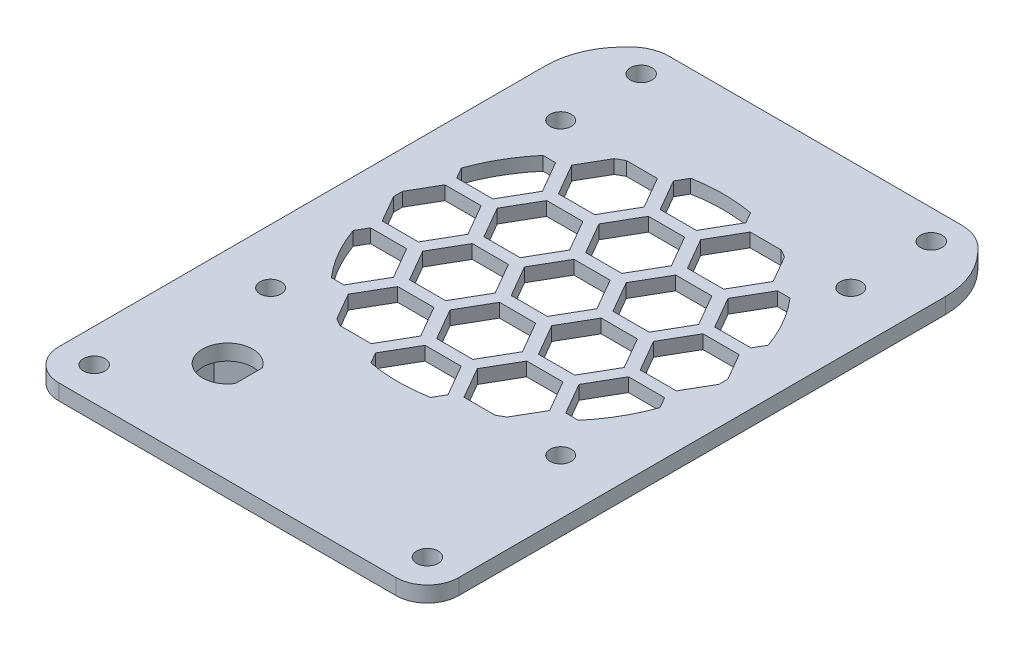
SolidWorks part; units mm, degrees
ref_plane "Front Plane" through (0, 0, 0) normal (0, 0, 1) x (1, 0, 0)
ref_plane "Top Plane" through (0, 0, 0) normal (0, 1, 0) x (1, 0, 0)
ref_plane "Right Plane" through (0, 0, 0) normal (1, 0, 0) x (0, 0, -1)
sketch "Sketch1" plane through (0, -8.5812, 0) normal (0, 1, 0) x (1, 0, 0)
  line L0 (-23.1823, 1.3362) -> (-42.1823, 1.3362)
  line L16 (-54.1823, -73.6638) -> (-11.1823, -73.6638)
  line L17 (-7.1823, -69.6638) -> (-7.1823, -7.6054)
  line L18 (-9.8717, -0.7822) -> (-11.849, 1.3362)
  line L19 (-11.849, 1.3362) -> (-23.1823, 1.3362)
  line L20 (-23.1823, 1.3362) -> (-23.1823, -1.1769)
  line L21 (-23.1823, -1.1769) -> (-10.589, -9.0704)
  line L22 (-9.1823, -11.6123) -> (-9.1823, -59.6638)
  line L23 (-9.1823, -59.6638) -> (-21.1823, -71.6638)
  line L24 (-21.1823, -71.6638) -> (-44.1823, -71.6638)
  line L25 (-44.1823, -71.6638) -> (-56.1823, -59.6638)
  line L26 (-56.1823, -59.6638) -> (-56.1823, -11.6123)
  line L27 (-54.7756, -9.0704) -> (-42.1823, -1.1769)
  line L28 (-42.1823, -1.1769) -> (-42.1823, 1.3362)
  line L29 (-42.1823, 1.3362) -> (-53.5156, 1.3362)
  line L30 (-53.5156, 1.3362) -> (-55.4928, -0.7822)
  line L31 (-58.1823, -7.6054) -> (-58.1823, -69.6638)
  line L32 (-54.1823, -73.6638) -> (-11.1823, -73.6638)
  line L33 (-7.1823, -69.6638) -> (-7.1823, -7.6054)
  line L34 (-9.8717, -0.7822) -> (-11.849, 1.3362)
  line L35 (-11.849, 1.3362) -> (-23.1823, 1.3362)
  line L36 (-23.1823, 1.3362) -> (-23.1823, -1.1769)
  line L37 (-23.1823, -1.1769) -> (-10.589, -9.0704)
  line L38 (-9.1823, -11.6123) -> (-9.1823, -59.6638)
  line L39 (-9.1823, -59.6638) -> (-21.1823, -71.6638)
  line L40 (-21.1823, -71.6638) -> (-44.1823, -71.6638)
  line L41 (-44.1823, -71.6638) -> (-56.1823, -59.6638)
  line L42 (-56.1823, -59.6638) -> (-56.1823, -11.6123)
  line L43 (-54.7756, -9.0704) -> (-42.1823, -1.1769)
  line L44 (-42.1823, -1.1769) -> (-42.1823, 1.3362)
  line L45 (-42.1823, 1.3362) -> (-53.5156, 1.3362)
  line L46 (-53.5156, 1.3362) -> (-55.4928, -0.7822)
  line L47 (-58.1823, -7.6054) -> (-58.1823, -69.6638)
  circle A0 centre (-14.1823, -2.3941) radius 1.375
  circle A1 centre (-51.1823, -2.3941) radius 1.375
  circle A2 centre (-11.4323, -69.4138) radius 1.375
  circle A3 centre (-53.9323, -69.4138) radius 1.375
  arc A6 (-11.1823, -73.6638) -> (-7.1823, -69.6638) centre (-11.1823, -69.6638) ccw
  arc A7 (-7.1823, -7.6054) -> (-9.8717, -0.7822) centre (-17.1823, -7.6054) ccw
  arc A8 (-9.1823, -11.6123) -> (-10.589, -9.0704) centre (-12.1823, -11.6123) ccw
  arc A9 (-54.7756, -9.0704) -> (-56.1823, -11.6123) centre (-53.1823, -11.6123) ccw
  arc A10 (-55.4928, -0.7822) -> (-58.1823, -7.6054) centre (-48.1823, -7.6054) ccw
  arc A11 (-58.1823, -69.6638) -> (-54.1823, -73.6638) centre (-54.1823, -69.6638) ccw
  arc A12 (-11.1823, -73.6638) -> (-7.1823, -69.6638) centre (-11.1823, -69.6638) ccw
  arc A13 (-7.1823, -7.6054) -> (-9.8717, -0.7822) centre (-17.1823, -7.6054) ccw
  arc A14 (-9.1823, -11.6123) -> (-10.589, -9.0704) centre (-12.1823, -11.6123) ccw
  arc A15 (-54.7756, -9.0704) -> (-56.1823, -11.6123) centre (-53.1823, -11.6123) ccw
  arc A16 (-55.4928, -0.7822) -> (-58.1823, -7.6054) centre (-48.1823, -7.6054) ccw
  arc A17 (-58.1823, -69.6638) -> (-54.1823, -73.6638) centre (-54.1823, -69.6638) ccw
  circle M24 centre (-51.1823, -2.3941) radius 2.3
  circle M25 centre (-11.4323, -69.4138) radius 2.3
  circle M26 centre (-53.9323, -69.4138) radius 2.3
  circle M27 centre (-14.1823, -2.3941) radius 2.3
  line M28 (-54.1823, -73.6638) -> (-11.1823, -73.6638)
  arc M29 (-11.1823, -73.6638) -> (-7.1823, -69.6638) centre (-11.1823, -69.6638) ccw
  line M30 (-7.1823, -69.6638) -> (-7.1823, -7.6054)
  arc M31 (-7.1823, -7.6054) -> (-9.8717, -0.7822) centre (-17.1823, -7.6054) ccw
  line M32 (-9.8717, -0.7822) -> (-11.849, 1.3362)
  line M33 (-11.849, 1.3362) -> (-23.1823, 1.3362)
  line M34 (-23.1823, 1.3362) -> (-23.1823, -1.1769)
  line M35 (-23.1823, -1.1769) -> (-10.589, -9.0704)
  arc M36 (-10.589, -9.0704) -> (-9.1823, -11.6123) centre (-12.1823, -11.6123) cw
  line M37 (-9.1823, -11.6123) -> (-9.1823, -59.6638)
  line M38 (-9.1823, -59.6638) -> (-21.1823, -71.6638)
  line M39 (-21.1823, -71.6638) -> (-44.1823, -71.6638)
  line M40 (-44.1823, -71.6638) -> (-56.1823, -59.6638)
  line M41 (-56.1823, -59.6638) -> (-56.1823, -11.6123)
  arc M42 (-56.1823, -11.6123) -> (-54.7756, -9.0704) centre (-53.1823, -11.6123) cw
  line M43 (-54.7756, -9.0704) -> (-42.1823, -1.1769)
  line M44 (-42.1823, -1.1769) -> (-42.1823, 1.3362)
  line M45 (-42.1823, 1.3362) -> (-53.5156, 1.3362)
  line M46 (-53.5156, 1.3362) -> (-55.4928, -0.7822)
  arc M47 (-55.4928, -0.7822) -> (-58.1823, -7.6054) centre (-48.1823, -7.6054) ccw
  line M48 (-58.1823, -7.6054) -> (-58.1823, -69.6638)
  arc M49 (-58.1823, -69.6638) -> (-54.1823, -73.6638) centre (-54.1823, -69.6638) ccw
  dimension "D2" = 2.75
  dimension "D3" = 2.75
  dimension "D4" = 2.75
  dimension "D5" = 2.75
  dimension "D1" = 0
extrude "Boss-Extrude1" add sketch "Sketch1" along normal blind 2 contours M49 M28 M29 M30 M31 M32 M33 M34 M35 M36 M37 M38 M39 M40 M41 M42 M43 M44 M45 M46 M47 M48 M25 M27 M26 M24 | L0 M34 M44 M43 M42 M41 M40 M39 M38 M37 M36 M35 | A0 M27 | A1 M24 | A3 M26 | A2 M25 region at (-32.6823, -8.5812, 35.6933) region at (-17.5156, -8.5812, -0.4292) region at (-53.4172, -8.5812, 2.3941) region at (-13.6672, -8.5812, 69.4138) region at (-56.1672, -8.5812, 69.4138) region at (-16.4172, -8.5812, 2.3941)
fillet "Fillet1" radius 5 2 edges at (-11.849, -7.5812, -1.3362) (-53.5156, -7.5812, -1.3362)
sketch "Sketch2" plane through (0, -6.5812, 0) normal (0, 1, 0) x (1, 0, 0)
  circle A1 centre (-32.6823, -31.1638) radius 20.75
  circle A2 centre (-32.6823, -31.1638) radius 20.75
  dimension "D1" = 0
extrude "Cut-Extrude1" cut sketch "Sketch2" against normal through all
sketch "Sketch3" plane through (0, -8.5812, 0) normal (0, -1, 0) x (1, 0, 0)
  circle A2 centre (-32.6823, 31.1638) radius 21.75
  circle A3 centre (-32.6823, 31.1638) radius 21.75
  dimension "D1" = 1
extrude "Cut-Extrude2" cut sketch "Sketch3" against normal blind 0.25
sketch "Sketch4" plane through (0, -6.5812, 0) normal (0, 1, 0) x (1, 0, 0)
  line L0 (-49.1368, -12.1638) -> (-40.9095, -16.9138) construction
  line L1 (-38.6001, -12.9138) -> (-43.2189, -12.9138)
  line L2 (-43.2189, -12.9138) -> (-45.5283, -16.9138)
  line L3 (-45.5283, -16.9138) -> (-43.2189, -20.9138)
  line L4 (-43.2189, -20.9138) -> (-38.6001, -20.9138)
  line L5 (-38.6001, -20.9138) -> (-36.2907, -16.9138)
  line L6 (-36.2907, -16.9138) -> (-38.6001, -12.9138)
  line L7 (-44.518, -12.1638) -> (-46.8274, -8.1638)
  line L8 (-46.8274, -8.1638) -> (-51.4462, -8.1638)
  line L9 (-51.4462, -8.1638) -> (-53.7556, -12.1638)
  line L10 (-53.7556, -12.1638) -> (-51.4462, -16.1638)
  line L11 (-51.4462, -16.1638) -> (-46.8274, -16.1638)
  line L12 (-46.8274, -16.1638) -> (-44.518, -12.1638)
  line L13 (-22.1456, -12.9138) -> (-26.7644, -12.9138)
  line L14 (-26.7644, -12.9138) -> (-29.0738, -16.9138)
  line L15 (-29.0738, -16.9138) -> (-26.7644, -20.9138)
  line L16 (-26.7644, -20.9138) -> (-22.1456, -20.9138)
  line L17 (-22.1456, -20.9138) -> (-19.8362, -16.9138)
  line L18 (-19.8362, -16.9138) -> (-22.1456, -12.9138)
  line L19 (-28.0635, -12.1638) -> (-30.3729, -8.1638)
  line L20 (-34.9917, -8.1638) -> (-37.3011, -12.1638)
  line L21 (-37.3011, -12.1638) -> (-34.9917, -16.1638)
  line L22 (-34.9917, -16.1638) -> (-30.3729, -16.1638)
  line L23 (-30.3729, -16.1638) -> (-28.0635, -12.1638)
  line L24 (-32.6823, -12.1638) -> (-24.455, -16.9138) construction
  line L25 (-30.3729, -8.1638) -> (-34.9917, -8.1638)
  line L26 (-5.6912, -12.9138) -> (-10.31, -12.9138)
  line L27 (-10.31, -12.9138) -> (-12.6194, -16.9138)
  line L28 (-12.6194, -16.9138) -> (-10.31, -20.9138)
  line L29 (-10.31, -20.9138) -> (-5.6912, -20.9138)
  line L30 (-5.6912, -20.9138) -> (-3.3818, -16.9138)
  line L31 (-3.3818, -16.9138) -> (-5.6912, -12.9138)
  line L32 (-11.609, -12.1638) -> (-13.9184, -8.1638)
  line L33 (-18.5372, -8.1638) -> (-20.8466, -12.1638)
  line L34 (-20.8466, -12.1638) -> (-18.5372, -16.1638)
  line L35 (-18.5372, -16.1638) -> (-13.9184, -16.1638)
  line L36 (-13.9184, -16.1638) -> (-11.609, -12.1638)
  line L37 (-16.2278, -12.1638) -> (-8.0006, -16.9138) construction
  line L38 (-13.9184, -8.1638) -> (-18.5372, -8.1638)
  line L39 (-22.1456, -22.4138) -> (-26.7644, -22.4138)
  line L40 (-26.7644, -22.4138) -> (-29.0738, -26.4138)
  line L41 (-29.0738, -26.4138) -> (-26.7644, -30.4138)
  line L42 (-26.7644, -30.4138) -> (-22.1456, -30.4138)
  line L43 (-22.1456, -30.4138) -> (-19.8362, -26.4138)
  line L44 (-19.8362, -26.4138) -> (-22.1456, -22.4138)
  line L45 (-28.0635, -21.6638) -> (-30.3729, -17.6638)
  line L46 (-34.9917, -17.6638) -> (-37.3011, -21.6638)
  line L47 (-37.3011, -21.6638) -> (-34.9917, -25.6638)
  line L48 (-34.9917, -25.6638) -> (-30.3729, -25.6638)
  line L49 (-30.3729, -25.6638) -> (-28.0635, -21.6638)
  line L50 (-32.6823, -21.6638) -> (-24.455, -26.4138) construction
  line L51 (-30.3729, -17.6638) -> (-34.9917, -17.6638)
  line L52 (-5.6912, -22.4138) -> (-10.31, -22.4138)
  line L53 (-10.31, -22.4138) -> (-12.6194, -26.4138)
  line L54 (-12.6194, -26.4138) -> (-10.31, -30.4138)
  line L55 (-10.31, -30.4138) -> (-5.6912, -30.4138)
  line L56 (-5.6912, -30.4138) -> (-3.3818, -26.4138)
  line L57 (-3.3818, -26.4138) -> (-5.6912, -22.4138)
  line L58 (-11.609, -21.6638) -> (-13.9184, -17.6638)
  line L59 (-18.5372, -17.6638) -> (-20.8466, -21.6638)
  line L60 (-20.8466, -21.6638) -> (-18.5372, -25.6638)
  line L61 (-18.5372, -25.6638) -> (-13.9184, -25.6638)
  line L62 (-13.9184, -25.6638) -> (-11.609, -21.6638)
  line L63 (-16.2278, -21.6638) -> (-8.0006, -26.4138) construction
  line L64 (-13.9184, -17.6638) -> (-18.5372, -17.6638)
  line L65 (-22.1456, -31.9138) -> (-26.7644, -31.9138)
  line L66 (-26.7644, -31.9138) -> (-29.0738, -35.9138)
  line L67 (-29.0738, -35.9138) -> (-26.7644, -39.9138)
  line L68 (-26.7644, -39.9138) -> (-22.1456, -39.9138)
  line L69 (-22.1456, -39.9138) -> (-19.8362, -35.9138)
  line L70 (-19.8362, -35.9138) -> (-22.1456, -31.9138)
  line L71 (-28.0635, -31.1638) -> (-30.3729, -27.1638)
  line L72 (-34.9917, -27.1638) -> (-37.3011, -31.1638)
  line L73 (-37.3011, -31.1638) -> (-34.9917, -35.1638)
  line L74 (-34.9917, -35.1638) -> (-30.3729, -35.1638)
  line L75 (-30.3729, -35.1638) -> (-28.0635, -31.1638)
  line L76 (-32.6823, -31.1638) -> (-24.455, -35.9138) construction
  line L77 (-30.3729, -27.1638) -> (-34.9917, -27.1638)
  line L78 (-5.6912, -31.9138) -> (-10.31, -31.9138)
  line L79 (-10.31, -31.9138) -> (-12.6194, -35.9138)
  line L80 (-12.6194, -35.9138) -> (-10.31, -39.9138)
  line L81 (-10.31, -39.9138) -> (-5.6912, -39.9138)
  line L82 (-5.6912, -39.9138) -> (-3.3818, -35.9138)
  line L83 (-3.3818, -35.9138) -> (-5.6912, -31.9138)
  line L84 (-11.609, -31.1638) -> (-13.9184, -27.1638)
  line L85 (-18.5372, -27.1638) -> (-20.8466, -31.1638)
  line L86 (-20.8466, -31.1638) -> (-18.5372, -35.1638)
  line L87 (-18.5372, -35.1638) -> (-13.9184, -35.1638)
  line L88 (-13.9184, -35.1638) -> (-11.609, -31.1638)
  line L89 (-16.2278, -31.1638) -> (-8.0006, -35.9138) construction
  line L90 (-13.9184, -27.1638) -> (-18.5372, -27.1638)
  line L91 (-22.1456, -41.4138) -> (-26.7644, -41.4138)
  line L92 (-26.7644, -41.4138) -> (-29.0738, -45.4138)
  line L93 (-29.0738, -45.4138) -> (-26.7644, -49.4138)
  line L94 (-26.7644, -49.4138) -> (-22.1456, -49.4138)
  line L95 (-22.1456, -49.4138) -> (-19.8362, -45.4138)
  line L96 (-19.8362, -45.4138) -> (-22.1456, -41.4138)
  line L97 (-28.0635, -40.6638) -> (-30.3729, -36.6638)
  line L98 (-34.9917, -36.6638) -> (-37.3011, -40.6638)
  line L99 (-37.3011, -40.6638) -> (-34.9917, -44.6638)
  line L100 (-34.9917, -44.6638) -> (-30.3729, -44.6638)
  line L101 (-30.3729, -44.6638) -> (-28.0635, -40.6638)
  line L102 (-32.6823, -40.6638) -> (-24.455, -45.4138) construction
  line L103 (-30.3729, -36.6638) -> (-34.9917, -36.6638)
  line L104 (-5.6912, -41.4138) -> (-10.31, -41.4138)
  line L105 (-10.31, -41.4138) -> (-12.6194, -45.4138)
  line L106 (-12.6194, -45.4138) -> (-10.31, -49.4138)
  line L107 (-10.31, -49.4138) -> (-5.6912, -49.4138)
  line L108 (-5.6912, -49.4138) -> (-3.3818, -45.4138)
  line L109 (-3.3818, -45.4138) -> (-5.6912, -41.4138)
  line L110 (-11.609, -40.6638) -> (-13.9184, -36.6638)
  line L111 (-18.5372, -36.6638) -> (-20.8466, -40.6638)
  line L112 (-20.8466, -40.6638) -> (-18.5372, -44.6638)
  line L113 (-18.5372, -44.6638) -> (-13.9184, -44.6638)
  line L114 (-13.9184, -44.6638) -> (-11.609, -40.6638)
  line L115 (-16.2278, -40.6638) -> (-8.0006, -45.4138) construction
  line L116 (-13.9184, -36.6638) -> (-18.5372, -36.6638)
  line L117 (-22.1456, -50.9138) -> (-26.7644, -50.9138)
  line L118 (-26.7644, -50.9138) -> (-29.0738, -54.9138)
  line L119 (-29.0738, -54.9138) -> (-26.7644, -58.9138)
  line L120 (-26.7644, -58.9138) -> (-22.1456, -58.9138)
  line L121 (-22.1456, -58.9138) -> (-19.8362, -54.9138)
  line L122 (-19.8362, -54.9138) -> (-22.1456, -50.9138)
  line L123 (-28.0635, -50.1638) -> (-30.3729, -46.1638)
  line L124 (-34.9917, -46.1638) -> (-37.3011, -50.1638)
  line L125 (-37.3011, -50.1638) -> (-34.9917, -54.1638)
  line L126 (-34.9917, -54.1638) -> (-30.3729, -54.1638)
  line L127 (-30.3729, -54.1638) -> (-28.0635, -50.1638)
  line L128 (-32.6823, -50.1638) -> (-24.455, -54.9138) construction
  line L129 (-30.3729, -46.1638) -> (-34.9917, -46.1638)
  line L130 (-5.6912, -50.9138) -> (-10.31, -50.9138)
  line L131 (-10.31, -50.9138) -> (-12.6194, -54.9138)
  line L132 (-12.6194, -54.9138) -> (-10.31, -58.9138)
  line L133 (-10.31, -58.9138) -> (-5.6912, -58.9138)
  line L134 (-5.6912, -58.9138) -> (-3.3818, -54.9138)
  line L135 (-3.3818, -54.9138) -> (-5.6912, -50.9138)
  line L136 (-11.609, -50.1638) -> (-13.9184, -46.1638)
  line L137 (-18.5372, -46.1638) -> (-20.8466, -50.1638)
  line L138 (-20.8466, -50.1638) -> (-18.5372, -54.1638)
  line L139 (-18.5372, -54.1638) -> (-13.9184, -54.1638)
  line L140 (-13.9184, -54.1638) -> (-11.609, -50.1638)
  line L141 (-16.2278, -50.1638) -> (-8.0006, -54.9138) construction
  line L142 (-13.9184, -46.1638) -> (-18.5372, -46.1638)
  line L143 (-38.6001, -22.4138) -> (-43.2189, -22.4138)
  line L144 (-43.2189, -22.4138) -> (-45.5283, -26.4138)
  line L145 (-45.5283, -26.4138) -> (-43.2189, -30.4138)
  line L146 (-43.2189, -30.4138) -> (-38.6001, -30.4138)
  line L147 (-38.6001, -30.4138) -> (-36.2907, -26.4138)
  line L148 (-36.2907, -26.4138) -> (-38.6001, -22.4138)
  line L149 (-44.518, -21.6638) -> (-46.8274, -17.6638)
  line L150 (-51.4462, -17.6638) -> (-53.7556, -21.6638)
  line L151 (-53.7556, -21.6638) -> (-51.4462, -25.6638)
  line L152 (-51.4462, -25.6638) -> (-46.8274, -25.6638)
  line L153 (-46.8274, -25.6638) -> (-44.518, -21.6638)
  line L154 (-49.1368, -21.6638) -> (-40.9095, -26.4138) construction
  line L155 (-46.8274, -17.6638) -> (-51.4462, -17.6638)
  line L156 (-38.6001, -31.9138) -> (-43.2189, -31.9138)
  line L157 (-43.2189, -31.9138) -> (-45.5283, -35.9138)
  line L158 (-45.5283, -35.9138) -> (-43.2189, -39.9138)
  line L159 (-43.2189, -39.9138) -> (-38.6001, -39.9138)
  line L160 (-38.6001, -39.9138) -> (-36.2907, -35.9138)
  line L161 (-36.2907, -35.9138) -> (-38.6001, -31.9138)
  line L162 (-44.518, -31.1638) -> (-46.8274, -27.1638)
  line L163 (-51.4462, -27.1638) -> (-53.7556, -31.1638)
  line L164 (-53.7556, -31.1638) -> (-51.4462, -35.1638)
  line L165 (-51.4462, -35.1638) -> (-46.8274, -35.1638)
  line L166 (-46.8274, -35.1638) -> (-44.518, -31.1638)
  line L167 (-49.1368, -31.1638) -> (-40.9095, -35.9138) construction
  line L168 (-46.8274, -27.1638) -> (-51.4462, -27.1638)
  line L169 (-38.6001, -41.4138) -> (-43.2189, -41.4138)
  line L170 (-43.2189, -41.4138) -> (-45.5283, -45.4138)
  line L171 (-45.5283, -45.4138) -> (-43.2189, -49.4138)
  line L172 (-43.2189, -49.4138) -> (-38.6001, -49.4138)
  line L173 (-38.6001, -49.4138) -> (-36.2907, -45.4138)
  line L174 (-36.2907, -45.4138) -> (-38.6001, -41.4138)
  line L175 (-44.518, -40.6638) -> (-46.8274, -36.6638)
  line L176 (-51.4462, -36.6638) -> (-53.7556, -40.6638)
  line L177 (-53.7556, -40.6638) -> (-51.4462, -44.6638)
  line L178 (-51.4462, -44.6638) -> (-46.8274, -44.6638)
  line L179 (-46.8274, -44.6638) -> (-44.518, -40.6638)
  line L180 (-49.1368, -40.6638) -> (-40.9095, -45.4138) construction
  line L181 (-46.8274, -36.6638) -> (-51.4462, -36.6638)
  line L182 (-38.6001, -50.9138) -> (-43.2189, -50.9138)
  line L183 (-43.2189, -50.9138) -> (-45.5283, -54.9138)
  line L184 (-45.5283, -54.9138) -> (-43.2189, -58.9138)
  line L185 (-43.2189, -58.9138) -> (-38.6001, -58.9138)
  line L186 (-38.6001, -58.9138) -> (-36.2907, -54.9138)
  line L187 (-36.2907, -54.9138) -> (-38.6001, -50.9138)
  line L188 (-44.518, -50.1638) -> (-46.8274, -46.1638)
  line L189 (-51.4462, -46.1638) -> (-53.7556, -50.1638)
  line L190 (-53.7556, -50.1638) -> (-51.4462, -54.1638)
  line L191 (-51.4462, -54.1638) -> (-46.8274, -54.1638)
  line L192 (-46.8274, -54.1638) -> (-44.518, -50.1638)
  line L193 (-49.1368, -50.1638) -> (-40.9095, -54.9138) construction
  line L194 (-46.8274, -46.1638) -> (-51.4462, -46.1638)
  circle A0 centre (-40.9095, -16.9138) radius 4 construction
  circle A1 centre (-49.1368, -12.1638) radius 4 construction
  circle A2 centre (-24.455, -16.9138) radius 4 construction
  circle A3 centre (-32.6823, -12.1638) radius 4 construction
  circle A4 centre (-8.0006, -16.9138) radius 4 construction
  circle A5 centre (-16.2278, -12.1638) radius 4 construction
  circle A6 centre (-24.455, -26.4138) radius 4 construction
  circle A7 centre (-32.6823, -21.6638) radius 4 construction
  circle A8 centre (-8.0006, -26.4138) radius 4 construction
  circle A9 centre (-16.2278, -21.6638) radius 4 construction
  circle A10 centre (-24.455, -35.9138) radius 4 construction
  circle A11 centre (-32.6823, -31.1638) radius 4 construction
  circle A12 centre (-8.0006, -35.9138) radius 4 construction
  circle A13 centre (-16.2278, -31.1638) radius 4 construction
  circle A14 centre (-24.455, -45.4138) radius 4 construction
  circle A15 centre (-32.6823, -40.6638) radius 4 construction
  circle A16 centre (-8.0006, -45.4138) radius 4 construction
  circle A17 centre (-16.2278, -40.6638) radius 4 construction
  circle A18 centre (-24.455, -54.9138) radius 4 construction
  circle A19 centre (-32.6823, -50.1638) radius 4 construction
  circle A20 centre (-8.0006, -54.9138) radius 4 construction
  circle A21 centre (-16.2278, -50.1638) radius 4 construction
  circle A22 centre (-40.9095, -26.4138) radius 4 construction
  circle A23 centre (-49.1368, -21.6638) radius 4 construction
  circle A24 centre (-40.9095, -35.9138) radius 4 construction
  circle A25 centre (-49.1368, -31.1638) radius 4 construction
  circle A26 centre (-40.9095, -45.4138) radius 4 construction
  circle A27 centre (-49.1368, -40.6638) radius 4 construction
  circle A28 centre (-40.9095, -54.9138) radius 4 construction
  circle A29 centre (-49.1368, -50.1638) radius 4 construction
  circle A32 centre (-32.6823, -31.1638) radius 20.75
  point P21 (-40.9095, -20.9138)
  point P243 (-32.6823, -31.1638)
  circle M226 centre (-32.6823, -31.1638) radius 20.75
  dimension "D1" = 8
  dimension "D2" = 1.5
  dimension "D5" = 1.5
  dimension "D6" = 1.5
  dimension "D3" = 3
  dimension "D4" = 5
extrude "Boss-Extrude2" add sketch "Sketch4" against normal up to surface (1.75 mm away) contours L194 L188 L171 L170 L169 L174 L173 L172 L182 L187 L125 L124 L129 L123 L127 L118 L117 L94 L93 L92 L91 L96 L95 L137 L142 L113 L112 L111 L116 L110 L80 L79 L88 L87 L86 L85 L90 L84 L54 L53 M226 | L11 L12 M226 | L188 L194 M226 | L142 L137 M226 | L34 L35 M226 | L187 L182 M226 | L117 L118 M226 | L79 L80 M226 | L53 L54 M226 region at (-40.5783, -6.5812, 12.332) region at (-46.817, -6.5812, 16.0338) region at (-18.5475, -6.5812, 16.0338) region at (-12.5119, -6.5812, 26.4878) region at (-46.817, -6.5812, 46.2938) region at (-12.5119, -6.5812, 35.8398) region at (-38.7179, -6.5812, 50.9699) region at (-18.5475, -6.5812, 46.2938) region at (-26.6467, -6.5812, 50.9699) up to face at (-32.6823, -8.3312, 9.4138)
sketch "Sketch8" plane through (0, -6.5812, 0) normal (0, 1, 0) x (1, 0, 0)
  line L0 (-42.8661, -59.045) -> (-42.8661, -62.4801)
  circle A0 centre (-45.5661, -60.7626) radius 3.2
  dimension "D1" = 6.4
  dimension "D2" = 2.7
extrude "Cut-Extrude3" cut sketch "Sketch8" against normal through all contours L0 A0 region at (-45.675, -6.5812, 60.7626)
sketch "Sketch9" plane through (0, -8.5812, 0) normal (0, -1, 0) x (1, 0, 0)
  line L0 (-42.8661, 59.045) -> (-42.8661, 62.4801) construction
  line L1 (-41.3911, 58.3522) -> (-41.3911, 63.173)
  line L2 (-41.3911, 63.173) -> (-45.5661, 65.5835)
  line L3 (-45.5661, 65.5835) -> (-49.7411, 63.173)
  line L4 (-49.7411, 63.173) -> (-49.7411, 58.3522)
  line L5 (-49.7411, 58.3522) -> (-45.5661, 55.9417)
  line L6 (-45.5661, 55.9417) -> (-41.3911, 58.3522)
  circle A0 centre (-45.5661, 60.7626) radius 4.175 construction
  circle A1 centre (-45.5661, 60.7626) radius 6
  dimension "D2" = 12
  dimension "D1" = 8.35
extrude "Boss-Extrude3" add sketch "Sketch9" along normal blind 5 contours A1 L6 L5 L4 L3 L2 L1 region at (-51.3964, -8.5812, 60.7626)
sketch "Sketch10" plane through (0, -6.5812, 0) normal (0, 1, 0) x (1, 0, 0)
  circle A0 centre (-14.1823, -49.6638) radius 1.5 construction
  circle A1 centre (-14.1823, -12.6638) radius 1.5 construction
  circle A2 centre (-51.1823, -12.6638) radius 1.5 construction
  circle A3 centre (-51.1823, -49.6638) radius 1.5 construction
  circle A4 centre (-14.1823, -49.6638) radius 1.5 construction
  circle A5 centre (-14.1823, -12.6638) radius 1.5 construction
  circle A6 centre (-51.1823, -12.6638) radius 1.5 construction
  circle A7 centre (-51.1823, -49.6638) radius 1.5 construction
  circle A8 centre (-14.1823, -49.6638) radius 1.35
  circle A9 centre (-51.1823, -49.6638) radius 1.35
  circle A10 centre (-51.1823, -12.6638) radius 1.35
  circle A11 centre (-14.1823, -12.6638) radius 1.35
  dimension "D1" = 2.7
  dimension "D2" = 2.7
  dimension "D3" = 2.7
  dimension "D4" = 2.7
extrude "Cut-Extrude4" cut sketch "Sketch10" against normal through all
